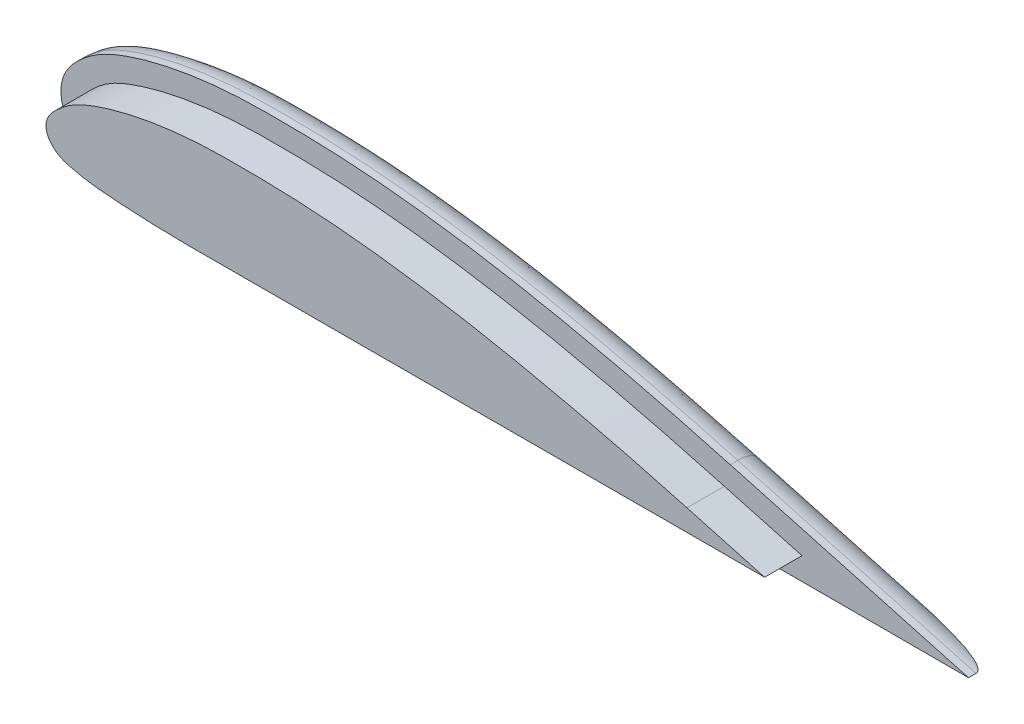
SolidWorks part; units mm, degrees
ref_plane "Front Plane" through (0, 0, 0) normal (0, 0, 1) x (1, 0, 0)
ref_plane "Top Plane" through (0, 0, 0) normal (0, 1, 0) x (1, 0, 0)
ref_plane "Right Plane" through (0, 0, 0) normal (1, 0, 0) x (0, 0, -1)
sketch "Sketch1" plane through (0, 0, 0) normal (0, 0, 1) x (1, 0, 0)
  line L4 (441.3938, 20.1125) -> (474.4331, 20.1125)
  line L5 (474.4331, 20.1125) -> (442.557, 28.8563)
  spline S2 degree 3 poles (442.557, 28.8563) (439.0727, 29.8121) (432.0999, 31.6716) (421.4868, 34.1106) (410.7798, 36.1975) (401.7202, 37.4887) (394.4128, 38.2045) (388.8653, 38.5359) (383.377, 38.6454) (378.7767, 38.631) (374.9635, 38.4319) (372.0662, 38.14) (369.2107, 37.707) (366.8278, 37.2314) (364.9084, 36.7539) (363.4799, 36.3495) (362.0564, 35.8958) (360.5728, 35.3529) (359.2877, 34.7841) (358.2164, 34.2146) (357.3891, 33.7069) (356.5526, 33.1031) (355.8208, 32.4753) (355.3545, 32.0442) (354.8557, 31.5528) (354.39, 31.0256) (353.965, 30.4492) (353.5863, 29.7672) (353.2277, 28.9329) (352.9613, 27.6499) (353.1116, 26.2983) (353.3653, 25.4506) (353.6956, 24.7529) (353.9982, 24.2624) (354.3478, 23.793) (354.7889, 23.3017) (355.3251, 22.8111) (356.056, 22.2868) (356.8397, 21.8718) (357.7655, 21.5068) (358.6401, 21.281) (359.288, 21.1303) (360.0698, 20.9562) (360.9049, 20.8056) (361.9719, 20.652) (363.214, 20.5264) (364.5787, 20.4101) (365.9782, 20.3046) (367.3787, 20.22) (369.229, 20.1314) (371.5307, 20.0564) (374.2712, 20.0109) (376.991, 19.9944) (379.6961, 19.9964) (383.2749, 20.0094) (387.735, 20.0177) (393.1045, 20.0244) (398.4705, 20.035) (403.8355, 20.0448) (410.9894, 20.058) (419.9315, 20.0736) (430.6622, 20.0933) (437.8166, 20.1056) (441.3938, 20.1125) knots 0 0 0 0 0.062498 0.124997 0.187495 0.249994 0.281243 0.312492 0.343742 0.374991 0.390615 0.40624 0.421865 0.437489 0.445302 0.453114 0.460926 0.468739 0.476551 0.480457 0.484363 0.488269 0.492175 0.496082 0.498035 0.499988 0.501941 0.502917 0.503894 0.505847 0.506824 0.5078 0.508777 0.509753 0.51073 0.511706 0.513659 0.515612 0.517566 0.519519 0.523425 0.527331 0.531237 0.535143 0.539049 0.546862 0.554674 0.562486 0.570299 0.578111 0.593736 0.60936 0.624985 0.640609 0.656234 0.687483 0.718732 0.749982 0.781231 0.81248 0.874979 0.937477 0.999976 0.999976 0.999976 0.999976
extrude "Boss-Extrude1" add sketch "Sketch1" along normal blind 10
fillet "Fillet1" radius 4 3 edges at (458.4951, 24.4844, 10) (457.9135, 20.1125, 10)
sketch "Sketch2" plane through (0, 0, 0) normal (0, 0, -1) x (-1, 0, 0)
  line L4 (-441.7634, 25.9631) -> (-452.1558, 23.1125)
  line L5 (-452.1558, 23.1125) -> (-441.3909, 23.1125)
  line L6 (-441.7634, 25.9631) -> (-452.1558, 23.1125)
  line L7 (-452.1558, 23.1125) -> (-441.3909, 23.1125)
  line L8 (-442.557, 28.8563) -> (-474.4331, 20.1125)
  line L9 (-474.4331, 20.1125) -> (-441.3938, 20.1125)
  line L10 (-442.557, 28.8563) -> (-474.4331, 20.1125)
  line L11 (-474.4331, 20.1125) -> (-441.3938, 20.1125)
  spline S2 degree 3 poles (-2884.3924, 1450.6573) (-2054.7336, 13.0638) (-1225.8234, 24.6115) (-393.1993, 23.0248) (-389.4923, 23.0208) (-383.9317, 23.0103) (-382.0782, 23.004) (-378.3711, 22.994) (-376.5176, 22.9932) (-372.8106, 23.0302) (-370.9571, 23.0679) (-368.1769, 23.1826) (-367.2509, 23.2302) (-365.4019, 23.3528) (-364.4785, 23.4259) (-363.0954, 23.554) (-362.6347, 23.6) (-361.7158, 23.7166) (-361.2575, 23.7874) (-360.5728, 23.9195) (-360.3451, 23.9686) (-359.89, 24.0707) (-359.6626, 24.123) (-359.21, 24.2333) (-358.984, 24.2896) (-358.5407, 24.4283) (-358.3225, 24.5084) (-357.8979, 24.7039) (-357.6895, 24.8196) (-357.3031, 25.0852) (-357.1213, 25.2328) (-356.8687, 25.4799) (-356.787, 25.566) (-356.6356, 25.7449) (-356.5657, 25.8382) (-356.3677, 26.1258) (-356.2583, 26.3349) (-356.0952, 26.7786) (-356.0486, 27.0088) (-356.0238, 27.4825) (-356.0548, 27.7144) (-356.1384, 28.0581) (-356.1729, 28.171) (-356.2602, 28.3875) (-356.3123, 28.4921) (-356.4256, 28.6971) (-356.4874, 28.7979) (-356.6194, 28.9904) (-356.6904, 29.082) (-356.9102, 29.3509) (-357.0677, 29.5202) (-357.3981, 29.8448) (-357.5667, 30.0039) (-357.9121, 30.3148) (-358.0871, 30.4672) (-358.4445, 30.7599) (-358.6278, 30.8992) (-359.19, 31.2975) (-359.5817, 31.5368) (-360.3915, 31.9741) (-360.81, 32.1743) (-362.0831, 32.7267) (-362.948, 33.031) (-364.6922, 33.5823) (-365.5719, 33.8275) (-367.3449, 34.2644) (-368.2385, 34.4546) (-370.0371, 34.79) (-370.9417, 34.9368) (-372.7619, 35.1863) (-373.6759, 35.2883) (-375.4974, 35.4473) (-376.4069, 35.5036) (-379.1328, 35.623) (-380.9467, 35.6387) (-384.5717, 35.6183) (-386.3832, 35.5876) (-390.0024, 35.4577) (-391.81, 35.3569) (-395.4218, 35.0866) (-397.2258, 34.9163) (-402.6333, 34.3225) (-406.2327, 33.8193) (-413.4213, 32.623) (-416.9976, 31.9312) (-424.1193, 30.4262) (-427.6665, 29.6139) (-587.2549, -9.896) (-715.1223, -171.9625) (-1555.7127, 2786.8732) knots -13.725361 -13.725361 -13.725361 -13.725361 0.25 0.25 0.3125 0.3125 0.34375 0.34375 0.375 0.375 0.40625 0.40625 0.421875 0.421875 0.4375 0.4375 0.445313 0.445313 0.453125 0.453125 0.457031 0.457031 0.460938 0.460938 0.464844 0.464844 0.46875 0.46875 0.472656 0.472656 0.476563 0.476563 0.478516 0.478516 0.480469 0.480469 0.484375 0.484375 0.488281 0.488281 0.492188 0.492188 0.494141 0.494141 0.496094 0.496094 0.498047 0.498047 0.5 0.5 0.503906 0.503906 0.507813 0.507813 0.511719 0.511719 0.515625 0.515625 0.523438 0.523438 0.53125 0.53125 0.546875 0.546875 0.5625 0.5625 0.578125 0.578125 0.59375 0.59375 0.609375 0.609375 0.625 0.625 0.65625 0.65625 0.6875 0.6875 0.71875 0.71875 0.75 0.75 0.8125 0.8125 0.875 0.875 0.9375 0.9375 3.698228 3.698228 3.698228 3.698228 only from (-441.3909, 23.1125) to (-441.7634, 25.9631)
  spline S3 degree 3 poles (-441.3909, 23.1125) (-426.5627, 23.0842) (-411.7345, 23.0602) (-393.1993, 23.0248) (-389.4923, 23.0208) (-383.9317, 23.0103) (-382.0782, 23.004) (-378.3711, 22.994) (-376.5176, 22.9932) (-372.8106, 23.0302) (-370.9571, 23.0679) (-368.1769, 23.1826) (-367.2509, 23.2302) (-365.4019, 23.3528) (-364.4785, 23.4259) (-363.0954, 23.554) (-362.6347, 23.6) (-361.7158, 23.7166) (-361.2575, 23.7874) (-360.5728, 23.9195) (-360.3451, 23.9686) (-359.89, 24.0707) (-359.6626, 24.123) (-359.21, 24.2333) (-358.984, 24.2896) (-358.5407, 24.4283) (-358.3225, 24.5084) (-357.8979, 24.7039) (-357.6895, 24.8196) (-357.3031, 25.0852) (-357.1213, 25.2328) (-356.8687, 25.4799) (-356.787, 25.566) (-356.6356, 25.7449) (-356.5657, 25.8382) (-356.3677, 26.1258) (-356.2583, 26.3349) (-356.0952, 26.7786) (-356.0486, 27.0088) (-356.0238, 27.4825) (-356.0548, 27.7144) (-356.1384, 28.0581) (-356.1729, 28.171) (-356.2602, 28.3875) (-356.3123, 28.4921) (-356.4256, 28.6971) (-356.4874, 28.7979) (-356.6194, 28.9904) (-356.6904, 29.082) (-356.9102, 29.3509) (-357.0677, 29.5202) (-357.3981, 29.8448) (-357.5667, 30.0039) (-357.9121, 30.3148) (-358.0871, 30.4672) (-358.4445, 30.7599) (-358.6278, 30.8992) (-359.19, 31.2975) (-359.5817, 31.5368) (-360.3915, 31.9741) (-360.81, 32.1743) (-362.0831, 32.7267) (-362.948, 33.031) (-364.6922, 33.5823) (-365.5719, 33.8275) (-367.3449, 34.2644) (-368.2385, 34.4546) (-370.0371, 34.79) (-370.9417, 34.9368) (-372.7619, 35.1863) (-373.6759, 35.2883) (-375.4974, 35.4473) (-376.4069, 35.5036) (-379.1328, 35.623) (-380.9467, 35.6387) (-384.5717, 35.6183) (-386.3832, 35.5876) (-390.0024, 35.4577) (-391.81, 35.3569) (-395.4218, 35.0866) (-397.2258, 34.9163) (-402.6333, 34.3225) (-406.2327, 33.8193) (-413.4213, 32.623) (-416.9976, 31.9312) (-424.1193, 30.4262) (-427.6665, 29.6139) (-434.7323, 27.8646) (-438.2508, 26.9267) (-441.7634, 25.9631) knots 0 0 0 0 0.25 0.25 0.3125 0.3125 0.34375 0.34375 0.375 0.375 0.40625 0.40625 0.421875 0.421875 0.4375 0.4375 0.445313 0.445313 0.453125 0.453125 0.457031 0.457031 0.460938 0.460938 0.464844 0.464844 0.46875 0.46875 0.472656 0.472656 0.476563 0.476563 0.478516 0.478516 0.480469 0.480469 0.484375 0.484375 0.488281 0.488281 0.492188 0.492188 0.494141 0.494141 0.496094 0.496094 0.498047 0.498047 0.5 0.5 0.503906 0.503906 0.507813 0.507813 0.511719 0.511719 0.515625 0.515625 0.523438 0.523438 0.53125 0.53125 0.546875 0.546875 0.5625 0.5625 0.578125 0.578125 0.59375 0.59375 0.609375 0.609375 0.625 0.625 0.65625 0.65625 0.6875 0.6875 0.71875 0.71875 0.75 0.75 0.8125 0.8125 0.875 0.875 0.9375 0.9375 1 1 1 1
  spline S4 degree 3 poles (-1244.353, 2624.291) (-1501.2387, 18.1594) (-960.5746, 21.0619) (-419.9315, 20.0736) (-410.9894, 20.058) (-403.8355, 20.0448) (-398.4705, 20.035) (-393.1045, 20.0244) (-387.735, 20.0177) (-383.2749, 20.0094) (-379.6961, 19.9964) (-376.991, 19.9944) (-374.2712, 20.0109) (-371.5307, 20.0564) (-369.229, 20.1314) (-367.3787, 20.22) (-365.9782, 20.3046) (-364.5787, 20.4101) (-363.214, 20.5264) (-361.9719, 20.652) (-360.9049, 20.8056) (-360.0698, 20.9562) (-359.288, 21.1303) (-358.6401, 21.281) (-357.7655, 21.5068) (-356.8397, 21.8718) (-356.056, 22.2868) (-355.3251, 22.8111) (-354.7889, 23.3017) (-354.3478, 23.793) (-353.9982, 24.2624) (-353.6956, 24.7529) (-353.3653, 25.4506) (-353.1116, 26.2983) (-352.9613, 27.6499) (-353.2277, 28.9329) (-353.5863, 29.7672) (-353.965, 30.4492) (-354.39, 31.0256) (-354.8557, 31.5528) (-355.3545, 32.0442) (-355.8208, 32.4753) (-356.5526, 33.1031) (-357.3891, 33.7069) (-358.2164, 34.2146) (-359.2877, 34.7841) (-360.5728, 35.3529) (-362.0564, 35.8958) (-363.4799, 36.3495) (-364.9084, 36.7539) (-366.8278, 37.2314) (-369.2107, 37.707) (-372.0662, 38.14) (-374.9635, 38.4319) (-378.7767, 38.631) (-383.377, 38.6454) (-388.8653, 38.5359) (-394.4128, 38.2045) (-401.7202, 37.4887) (-410.7798, 36.1975) (-421.4868, 34.1106) (-579.4195, -2.1837) (-684.9381, -148.8712) (-2575.8753, 2111.064) knots -9.259048 -9.259048 -9.259048 -9.259048 0.062498 0.124997 0.187495 0.218745 0.249994 0.281243 0.312492 0.343742 0.359366 0.374991 0.390615 0.40624 0.421865 0.429677 0.437489 0.445302 0.453114 0.460926 0.464832 0.468739 0.472645 0.476551 0.480457 0.48241 0.484363 0.486316 0.488269 0.489246 0.490222 0.491199 0.492175 0.493152 0.494129 0.496082 0.497058 0.498035 0.499988 0.501941 0.503894 0.5078 0.511706 0.515612 0.519519 0.523425 0.531237 0.539049 0.546862 0.554674 0.562486 0.578111 0.593736 0.60936 0.624985 0.656234 0.687483 0.718732 0.749982 0.81248 0.874979 0.937477 3.602583 3.602583 3.602583 3.602583 only from (-441.3938, 20.1125) to (-442.557, 28.8563)
  spline S5 degree 3 poles (-441.3938, 20.1125) (-437.8166, 20.1056) (-430.6622, 20.0933) (-419.9315, 20.0736) (-410.9894, 20.058) (-403.8355, 20.0448) (-398.4705, 20.035) (-393.1045, 20.0244) (-387.735, 20.0177) (-383.2749, 20.0094) (-379.6961, 19.9964) (-376.991, 19.9944) (-374.2712, 20.0109) (-371.5307, 20.0564) (-369.229, 20.1314) (-367.3787, 20.22) (-365.9782, 20.3046) (-364.5787, 20.4101) (-363.214, 20.5264) (-361.9719, 20.652) (-360.9049, 20.8056) (-360.0698, 20.9562) (-359.288, 21.1303) (-358.6401, 21.281) (-357.7655, 21.5068) (-356.8397, 21.8718) (-356.056, 22.2868) (-355.3251, 22.8111) (-354.7889, 23.3017) (-354.3478, 23.793) (-353.9982, 24.2624) (-353.6956, 24.7529) (-353.3653, 25.4506) (-353.1116, 26.2983) (-352.9613, 27.6499) (-353.2277, 28.9329) (-353.5863, 29.7672) (-353.965, 30.4492) (-354.39, 31.0256) (-354.8557, 31.5528) (-355.3545, 32.0442) (-355.8208, 32.4753) (-356.5526, 33.1031) (-357.3891, 33.7069) (-358.2164, 34.2146) (-359.2877, 34.7841) (-360.5728, 35.3529) (-362.0564, 35.8958) (-363.4799, 36.3495) (-364.9084, 36.7539) (-366.8278, 37.2314) (-369.2107, 37.707) (-372.0662, 38.14) (-374.9635, 38.4319) (-378.7767, 38.631) (-383.377, 38.6454) (-388.8653, 38.5359) (-394.4128, 38.2045) (-401.7202, 37.4887) (-410.7798, 36.1975) (-421.4868, 34.1106) (-432.0999, 31.6716) (-439.0727, 29.8121) (-442.557, 28.8563) knots 0 0 0 0 0.062498 0.124997 0.187495 0.218745 0.249994 0.281243 0.312492 0.343742 0.359366 0.374991 0.390615 0.40624 0.421865 0.429677 0.437489 0.445302 0.453114 0.460926 0.464832 0.468739 0.472645 0.476551 0.480457 0.48241 0.484363 0.486316 0.488269 0.489246 0.490222 0.491199 0.492175 0.493152 0.494129 0.496082 0.497058 0.498035 0.499988 0.501941 0.503894 0.5078 0.511706 0.515612 0.519519 0.523425 0.531237 0.539049 0.546862 0.554674 0.562486 0.578111 0.593736 0.60936 0.624985 0.656234 0.687483 0.718732 0.749982 0.81248 0.874979 0.937477 0.999976 0.999976 0.999976 0.999976
  dimension "D1" = 3
  dimension "D2" = 0
extrude "Cut-Extrude1" cut sketch "Sketch2" against normal blind 5
mirror "Mirror1" about plane through (354.3826, 30.9982, 0) normal (0, 0, -1) of bodies 102
delete or keep bodies "Body-Delete/Keep 1" type delete bodies bodies 102
